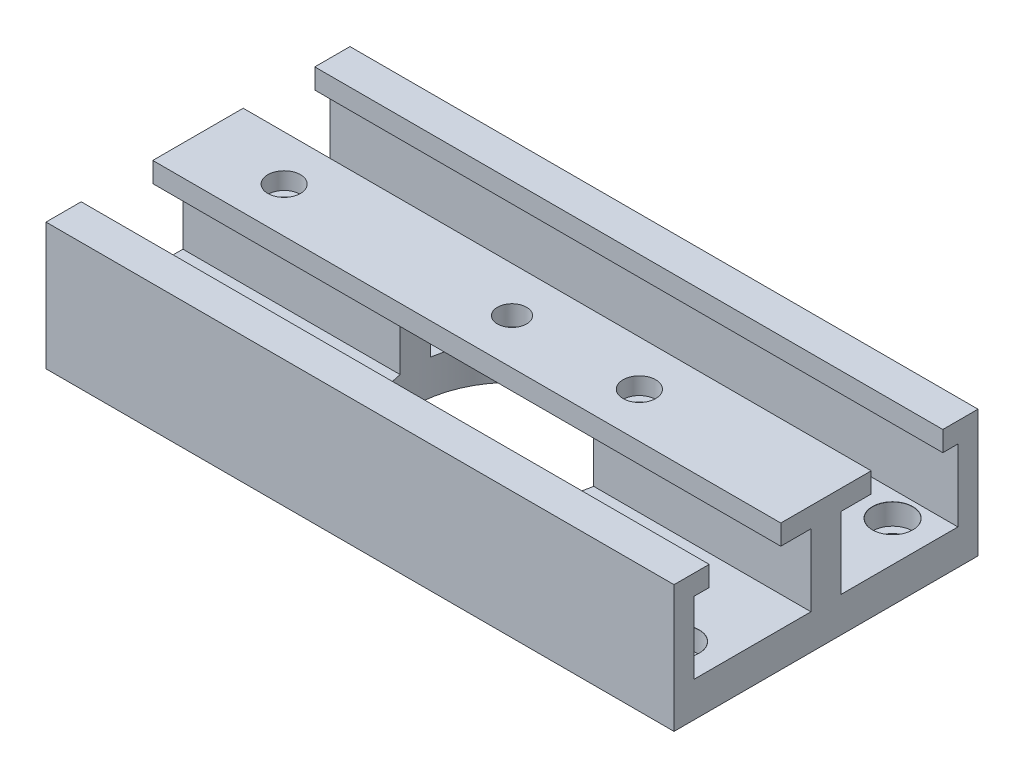
SolidWorks part; units mm, degrees
ref_plane "Front Plane" through (0, 0, 0) normal (0, 0, 1) x (1, 0, 0)
ref_plane "Top Plane" through (0, 0, 0) normal (0, 1, 0) x (1, 0, 0)
ref_plane "Right Plane" through (0, 0, 0) normal (1, 0, 0) x (0, 0, -1)
sketch "Sketch2" plane through (0, 0, 0) normal (1, 0, 0) x (0, 0, -1)
  line L0 (0, 0) -> (-30.25, 0)
  line L1 (-30.25, 0) -> (-30.25, 25.3)
  line L2 (-30.25, 25.3) -> (-23.25, 25.3)
  line L3 (-23.25, 25.3) -> (-23.25, 21.3)
  line L4 (-23.25, 21.3) -> (-26.25, 21.3)
  line L5 (-26.25, 21.3) -> (-26.25, 7)
  line L6 (-26.25, 7) -> (-3, 7)
  line L7 (-3, 7) -> (-3, 21.3)
  line L8 (-3, 21.3) -> (-9, 21.3)
  line L9 (-9, 21.3) -> (-9, 25.3)
  line L10 (-9, 25.3) -> (0, 25.3)
  line L11 (0, 25.3) -> (0, 0)
  line L12 (0, 25.3) -> (0, 26.2326) construction
  point P0 (-26.25, 14.15)
  point P3 (-23.25, 23.3)
  point P4 (0, 0)
  dimension "D1" = 52.5
  dimension "D2" = 6
  dimension "D3" = 18
  dimension "D4" = 3
  dimension "D5" = 4
  dimension "D6" = 14.3
  dimension "D7" = 7
  dimension "D8" = 4
extrude "Boss-Extrude1" add sketch "Sketch2" along normal blind 125 contours L7 L8 L9 L10 L11 L0 L1 L2 L3 L4 L5 L6
mirror "Mirror1" about plane through (0, 0, 0) normal (0, 0, 1) of "Boss-Extrude1"
sketch "Sketch4" plane through (0, 0, 0) normal (0, -1, 0) x (-1, 0, 0)
  line L0 (-125, -30.25) -> (0, 30.25) construction
  line L1 (0, -30.25) -> (-125, 30.25) construction
  circle A0 centre (-62.5, 0) radius 19.5
  circle A1 centre (-62.5, 0) radius 2.9
  dimension "D1" = 5.8
  dimension "D2" = 39
extrude "Cut-Extrude1" cut sketch "Sketch4" against normal up to surface (21.3 mm away) up to face at (62.5, 21.3, 6)
extrude "Cut-Extrude2" cut sketch "Sketch4<2>" against normal through all both and the other way through all contours A1 region at (62.5, 0, 0)
sketch "Sketch4<2>" plane through (0, 0, 0) normal (0, -1, 0) x (-1, 0, 0) same geometry as "Sketch4"
hole_wizard "CBORE for M4 Hex Socket Head Cap Screw1" positions "3DSketch1" profile "Sketch6" counterbore size "M4" standard "DIN" end condition through all
sketch3d "3DSketch1"
  line L0 (125, 7, 26.25) -> (0, 7, 26.25) construction
  line L1 (125, 7, 26.25) -> (125, 7, 3) construction
  line L2 (125, 7, -26.25) -> (125, 7, -3) construction
  line L3 (125, 7, -26.25) -> (0, 7, -26.25) construction
  line L4 (0, 7, -26.25) -> (0, 7, -3) construction
  line L5 (0, 7, 26.25) -> (0, 7, 3) construction
  line L6 (8, 7, -21.25) -> (123, 7, -21.25) construction
  line L8 (117, 7, 21.25) -> (2, 7, 21.25) construction
  point P0 (117, 7, 21.25)
  point P2 (117, 7, -21.25)
  point P4 (8, 7, -21.25)
  point P6 (8, 7, 21.25)
  point P21 (28, 7, 21.25)
  point P23 (97, 7, 21.25)
  point P25 (97, 7, -21.25)
  point P27 (28, 7, -21.25)
  dimension "D1" = 5
  dimension "D2" = 8
  dimension "D3" = 8
  dimension "D4" = 5
  dimension "D5" = 5
  dimension "D6" = 8
  dimension "D7" = 8
  dimension "D8" = 5
  dimension "D9" = 20
  dimension "D10" = 20
  dimension "D11" = 20
  dimension "D12" = 20
sketch "Sketch6" plane through (117, 7, 21.25) normal (1, 0, 0) x (0, 0, 1)
  line L0 (0, 0) -> (0, 7)
  line L1 (0, 7) -> (2.25, 7)
  line L3 (2.25, 7) -> (2.25, 4.2)
  line L4 (4, 4.2) -> (2.25, 4.2)
  line L5 (4, 4.2) -> (4, 0.025)
  line L6 (4, 0.025) -> (4.025, 0)
  line L7 (4.025, 0) -> (0, 0)
  line L8 (-4, 0.025) -> (-4.025, 0) construction
  line L11 (0, -6.35) -> (0, 107.95) construction
  dimension "Thru Hole Dia." = 4.5
  dimension "Thru Hole Depth" = 7
  dimension "C'Bore Dia." = 8
  dimension "C'Bore Depth" = 4.2
  dimension "Near C'Sink Dia." = 8.05
  dimension "Near C'Sink Angle" = 90
sketch "Sketch7" plane through (0, 7, 0) normal (0, 1, 0) x (1, 0, 0)
  line L1 (51.6072, -22.55) -> (15.2167, -22.55)
  line L2 (51.6072, -24.25) -> (15.2167, -24.25)
  line L5 (43.2322, -3) -> (0, -3)
  line L6 (0, -3) -> (0, -26.25)
  line L7 (0, -26.25) -> (125, -26.25)
  line L8 (125, -26.25) -> (125, -3)
  line L9 (125, -3) -> (81.7678, -3)
  line L10 (43.2322, -3) -> (0, -3)
  line L11 (0, -3) -> (0, -26.25)
  line L12 (0, -26.25) -> (125, -26.25)
  line L13 (125, -26.25) -> (125, -3)
  line L14 (125, -3) -> (81.7678, -3)
  arc A1 (43.2322, -3) -> (81.7678, -3) centre (62.5, 0) ccw
  arc A2 (43.2322, -3) -> (81.7678, -3) centre (62.5, 0) ccw
  arc A3 (51.6072, -24.25) -> (51.6072, -22.55) centre (51.6072, -23.4) ccw
  arc A4 (15.2167, -22.55) -> (14.3667, -23.4) centre (15.2167, -23.4) ccw
  arc A5 (14.3667, -23.4) -> (15.2167, -24.25) centre (15.2167, -23.4) ccw
  dimension "D1" = 0
sketch "Sketch8" plane through (0, 0, 0) normal (0, -1, 0) x (1, 0, 0)
  circle A1 centre (87.8491, 0) radius 1.5
  circle A3 centre (17.1509, 0) radius 1.5
sketch "Sketch10" plane through (0, 25.3, 0) normal (0, 1, 0) x (1, 0, 0)
  line L4 (0, 9) -> (0, -9)
  line L5 (0, -9) -> (125, -9)
  line L6 (125, -9) -> (125, 9)
  line L7 (125, 9) -> (0, 9)
  line L8 (0, 9) -> (0, -9)
  line L9 (0, -9) -> (125, -9)
  line L10 (125, -9) -> (125, 9)
  line L11 (125, 9) -> (0, 9)
  circle A0 centre (17.1509, 0) radius 1.5 construction
  circle A1 centre (17.1509, 0) radius 1.5
  circle A2 centre (87.8491, 0) radius 1.5 construction
  circle A3 centre (87.8491, 0) radius 1.5
  point P2 (17.1509, 0)
  point P7 (87.8491, 0)
  dimension "D1" = 0
hole_wizard "CBORE for M3 Hex Socket Head Cap Screw1" positions "Sketch10" profile "Sketch12" counterbore size "M3" standard "DIN" end condition through all
sketch "Sketch12" plane through (87.8491, 25.3, 0) normal (1, 0, 0) x (0, 0, 1)
  line L0 (0, 0) -> (0, 25.3)
  line L1 (0, 25.3) -> (1.7, 25.3)
  line L3 (1.7, 25.3) -> (1.7, 3.4)
  line L4 (1.7, 3.4) -> (3.25, 3.4)
  line L5 (3.25, 3.4) -> (3.25, 0)
  line L7 (3.25, 0) -> (0, 0)
  line L11 (0, -6.35) -> (0, 107.95) construction
  dimension "Thru Hole Dia." = 3.4
  dimension "Thru Hole Depth" = 25.3
  dimension "C'Bore Dia." = 6.5
  dimension "C'Bore Depth" = 3.4
